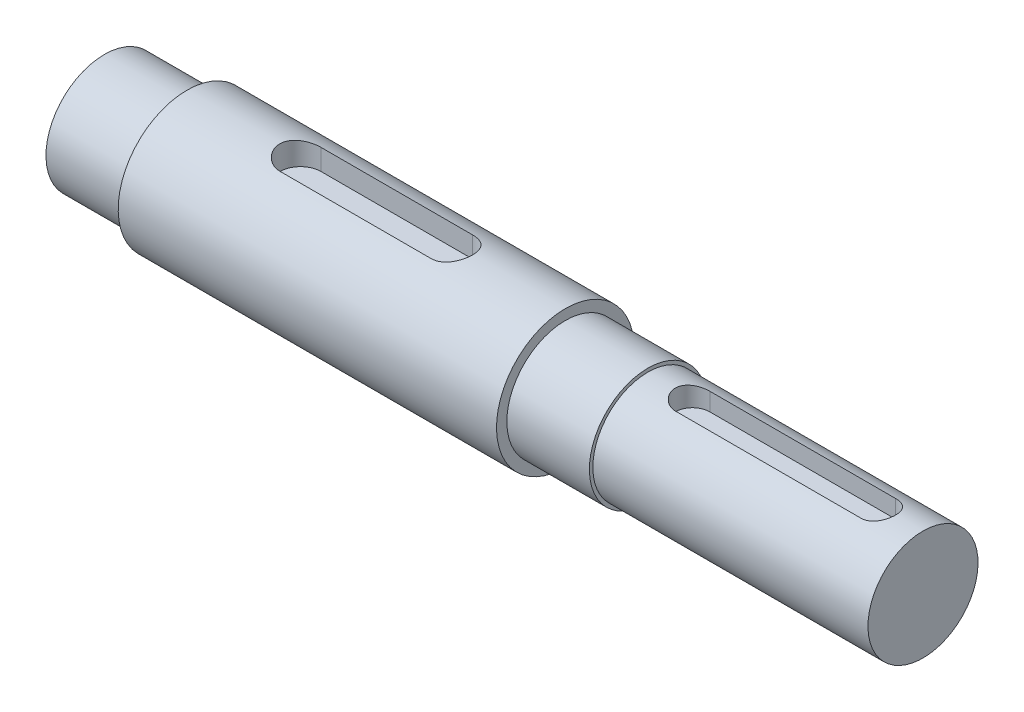
SolidWorks part; units mm, degrees
ref_plane "Спереди" through (0, 0, 0) normal (0, 0, 1) x (1, 0, 0)
ref_plane "Сверху" through (0, 0, 0) normal (0, 1, 0) x (1, 0, 0)
ref_plane "Справа" through (0, 0, 0) normal (1, 0, 0) x (0, 0, -1)
sketch "Эскиз1" plane through (0, 0, 0) normal (0, 0, 1) x (1, 0, 0)
  line L0 (0, 0) -> (0, 8.5)
  line L1 (0, 8.5) -> (12, 8.5)
  line L2 (12, 8.5) -> (12, 10)
  line L3 (12, 10) -> (67, 10)
  line L4 (67, 10) -> (67, 8.5)
  line L5 (67, 8.5) -> (79, 8.5)
  line L6 (79, 8.5) -> (79, 8)
  line L7 (79, 8) -> (119, 8)
  line L8 (119, 8) -> (119, 0)
  line L9 (119, 0) -> (0, 0) construction
  line L10 (0, 0) -> (119, 0)
  dimension "D1" = 17
  dimension "D2" = 20
  dimension "D3" = 17
  dimension "D4" = 16
  dimension "D5" = 12
  dimension "D6" = 55
  dimension "D7" = 40
  dimension "D9" = 12
revolve "Повернуть1" add sketch "Эскиз1" angle 360 about L9
sketch "Эскиз2" plane through (0, 0, 0) normal (0, 1, 0) x (1, 0, 0)
  line L3 (28.5, 0) -> (50.5, 0) construction
  line L6 (28.5, 3) -> (50.5, 3)
  line L7 (28.5, -3) -> (50.5, -3)
  arc A0 (28.5, 3) -> (28.5, -3) centre (28.5, 0) ccw
  arc A1 (50.5, -3) -> (50.5, 3) centre (50.5, 0) ccw
  point P9 (39.5, 0)
extrude "Вырез-Вытянуть1" cut sketch "Эскиз2" along normal through all from offset 6.5
sketch "Эскиз3" plane through (0, 0, 0) normal (0, 1, 0) x (1, 0, 0)
  line L3 (85.5, 0) -> (112.5, 0) construction
  line L5 (85.5, 2.5) -> (112.5, 2.5)
  line L6 (85.5, -2.5) -> (112.5, -2.5)
  arc A0 (85.5, 2.5) -> (85.5, -2.5) centre (85.5, 0) ccw
  arc A1 (112.5, -2.5) -> (112.5, 2.5) centre (112.5, 0) ccw
  point P9 (99, 0)
extrude "Вырез-Вытянуть2" cut sketch "Эскиз3" along normal through all from offset 5
